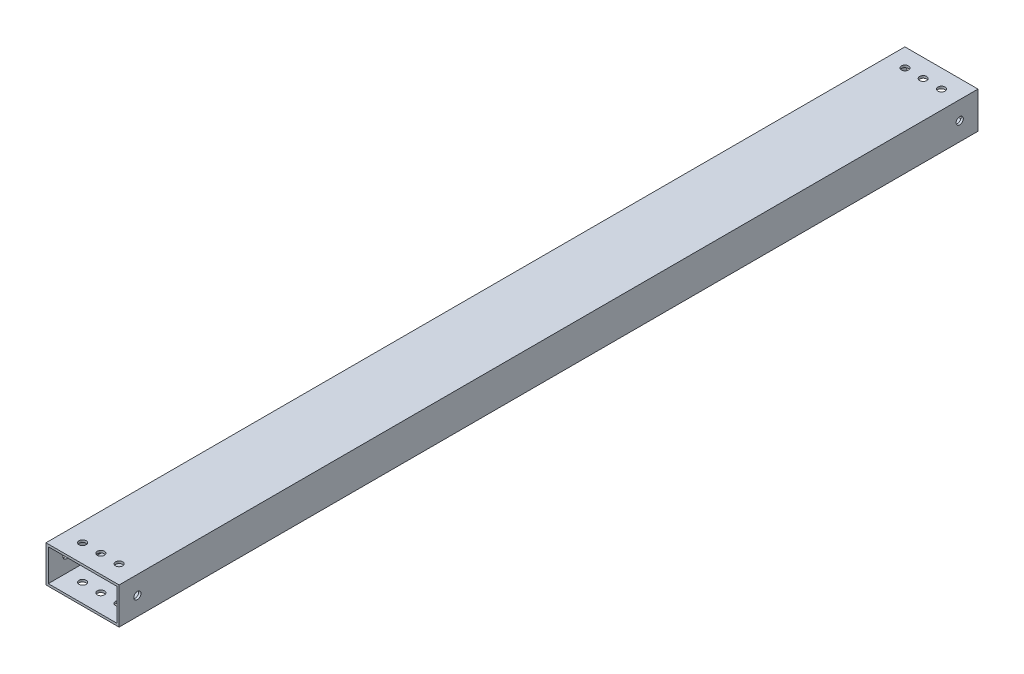
SolidWorks part; units mm, degrees
material "6061-T6 (SS)"
ref_plane "Front Plane" through (0, 0, 0) normal (0, 0, 1) x (1, 0, 0)
ref_plane "Top Plane" through (0, 0, 0) normal (0, 1, 0) x (1, 0, 0)
ref_plane "Right Plane" through (0, 0, 0) normal (1, 0, 0) x (0, 0, -1)
sketch "Sketch1" plane through (0, 0, 0) normal (0, 0, 1) x (1, 0, 0)
  line L1 (0, 0) -> (50.8, 0)
  line L2 (0, 0) -> (0, 25.4)
  line L3 (0, 25.4) -> (50.8, 25.4)
  line L4 (50.8, 0) -> (50.8, 25.4)
  dimension "D1" = 50.8
  dimension "D2" = 25.4
extrude "Boss-Extrude1" add sketch "Sketch1" along normal mid plane 596.9
shell "Shell1" thickness 1.5875 removed face at (25.4, 12.7, -298.45) removed face at (25.4, 12.7, 298.45)
sketch "Sketch2" plane through (0, 25.4, 0) normal (0, 1, 0) x (1, 0, 0)
  line L0 (50.8, -298.45) -> (50.8, 298.45) construction
  line L1 (50.8, -298.45) -> (0, -298.45) construction
  circle A0 centre (38.1, -285.75) radius 2.4892
  circle A1 centre (25.4, -285.75) radius 2.4892
  circle A2 centre (12.7, -285.75) radius 2.4892
  point P10 (0, 0)
  point P11 (0, 0)
  point P13 (27.8567, -288.6219)
  dimension "D1" = 4.9784
  dimension "D2" = 12.7
  dimension "D3" = 12.7
  dimension "D4" = 12.7
  dimension "D5" = 12.7
extrude "Cut-Extrude1" cut sketch "Sketch2" against normal through all
sketch "Sketch3" plane through (50.8, 0, 0) normal (1, 0, 0) x (0, 0, -1)
  line L0 (-298.45, 25.4) -> (298.45, 25.4) construction
  line L1 (-298.45, 0) -> (-298.45, 25.4) construction
  circle A0 centre (-285.75, 12.7) radius 2.4892
  dimension "D1" = 4.9784
  dimension "D2" = 12.7
  dimension "D3" = 12.7
extrude "Cut-Extrude2" cut sketch "Sketch3" against normal through all
mirror "Mirror1" about plane through (0, 0, 0) normal (0, 0, 1) of "Cut-Extrude1", "Cut-Extrude2"
